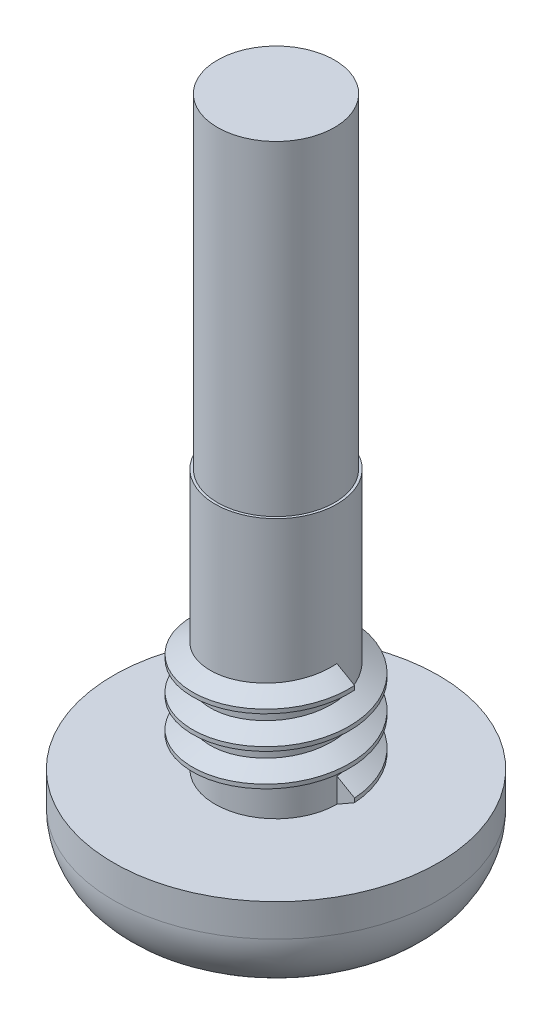
SolidWorks part; units mm, degrees
ref_plane "Front Plane" through (0, 0, 0) normal (0, 0, 1) x (1, 0, 0)
ref_plane "Top Plane" through (0, 0, 0) normal (0, 1, 0) x (1, 0, 0)
ref_plane "Right Plane" through (0, 0, 0) normal (1, 0, 0) x (0, 0, -1)
sketch "Sketch2" plane through (0, 0, 0) normal (0, 1, 0) x (1, 0, 0)
  circle A0 centre (0, 0) radius 6.35
  dimension "D1" = 12.7
extrude "Boss-Extrude1" add sketch "Sketch2" along normal blind 3.81
sketch "Sketch3" plane through (0, 3.81, 0) normal (0, 1, 0) x (1, 0, 0)
  circle A0 centre (0, 0) radius 2.3825
  dimension "D1" = 4.765
extrude "Boss-Extrude2" add sketch "Sketch3" along normal blind 22.86
thread "Thread2" pitch 1.27 method extrude profile "Thread Profile2" start angle 0, offset 0, length 3.81, pitch 1.27, diameter 4.765
ref_plane "Plane2" through (2.3825, 3.81, 0) normal (0, 0, 1) x (1, 0, 0)
sketch "Thread Profile2" plane through (2.3825, 3.81, 0) normal (0, 0, 1) x (1, 0, 0)
  line L0 (0, 0) -> (0, 1.27) construction
  line L1 (0, 0) -> (0.6874, 0.3969)
  line L2 (0.6874, 0.3969) -> (0.6874, 0.5556)
  line L3 (0.6874, 0.5556) -> (0, 0.9525)
  line L4 (0.6874, 0.4762) -> (0, 0.4762) construction
  line L11 (0, 0) -> (0, 0.9525)
  point P2 (0, 0)
  dimension "Pitch" = 1.27
  dimension "Profile_Angle" = 60
  dimension "Profile_Land" = 0.1588
  dimension "Profile_Height" = 0.6874
sketch "Sketch4" plane through (0, 26.67, 0) normal (0, 1, 0) x (1, 0, 0)
  circle A0 centre (0, 0) radius 2.286
  dimension "D1" = 4.572
extrude "Cut-Extrude1" cut sketch "Sketch4" against normal blind 12.7 flip side to cut
fillet "Fillet1" radius 2.54 1 edges at (0, 0, 6.35)
